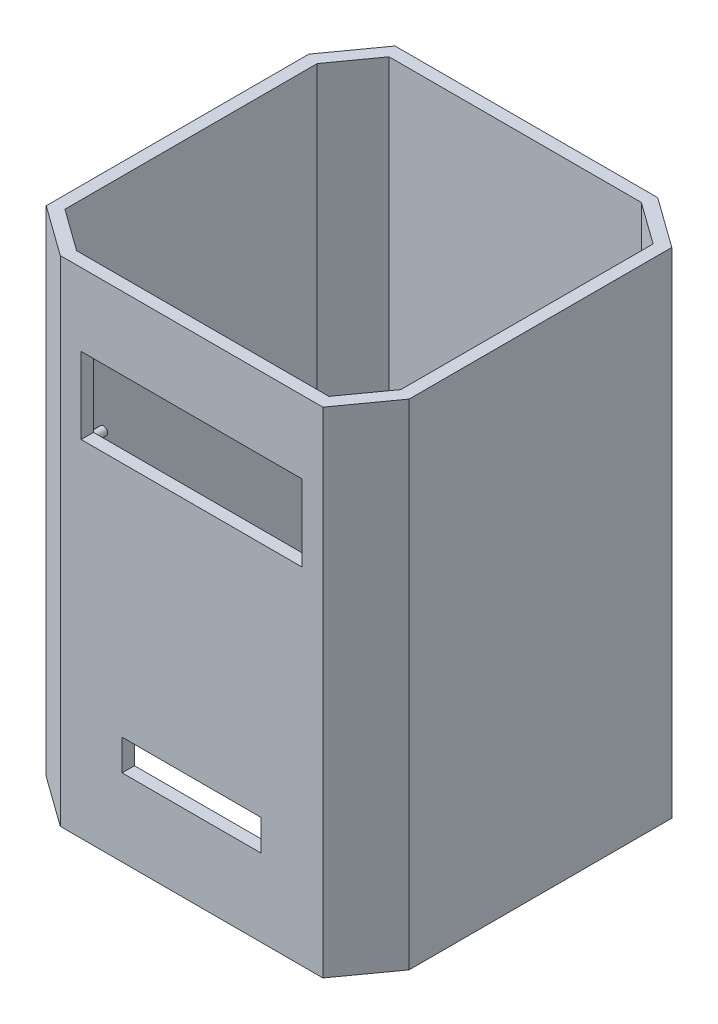
SolidWorks part; units mm, degrees
ref_plane "Front Plane" through (0, 0, 0) normal (0, 0, 1) x (1, 0, 0)
ref_plane "Top Plane" through (0, 0, 0) normal (0, 1, 0) x (1, 0, 0)
ref_plane "Right Plane" through (0, 0, 0) normal (1, 0, 0) x (0, 0, -1)
sketch "Sketch1" plane through (0, 0, 0) normal (0, 1, 0) x (1, 0, 0)
  line L0 (-66.6656, -62.9761) -> (18.3344, -62.9761)
  line L5 (18.3344, -62.9761) -> (30.0152, -46.7417)
  line L6 (30.0152, -46.7417) -> (30.0152, 38.2583)
  line L7 (30.0152, 38.2583) -> (13.7808, 49.9392)
  line L8 (13.7808, 49.9392) -> (-71.2192, 49.9392)
  line L9 (-71.2192, 49.9392) -> (-82.9001, 33.7047)
  line L10 (-82.9001, 33.7047) -> (-82.9001, -51.2953)
  line L11 (-82.9001, -51.2953) -> (-66.6656, -62.9761)
  dimension "D1" = 85
  dimension "D2" = 85
  dimension "D3" = 20
  dimension "D4" = 20
  dimension "D5" = 85
  dimension "D6" = 20
  dimension "D7" = 85
  dimension "D8" = 20
extrude "Boss-Extrude2" add sketch "Sketch1" along normal blind 160
sketch "Sketch10" plane through (0, 160, 0) normal (0, 1, 0) x (1, 0, 0)
  line L16 (-78.9001, -49.2455) -> (-65.3762, -58.9761)
  line L17 (-65.3762, -58.9761) -> (16.2846, -58.9761)
  line L18 (16.2846, -58.9761) -> (26.0152, -45.4522)
  line L19 (26.0152, -45.4522) -> (26.0152, 36.2086)
  line L20 (26.0152, 36.2086) -> (12.4913, 45.9392)
  line L21 (12.4913, 45.9392) -> (-69.1694, 45.9392)
  line L22 (-69.1694, 45.9392) -> (-78.9001, 32.4153)
  line L23 (-78.9001, 32.4153) -> (-78.9001, -49.2455)
  line L24 (-78.9001, -49.2455) -> (-65.3762, -58.9761)
  line L25 (-65.3762, -58.9761) -> (16.2846, -58.9761)
  line L26 (16.2846, -58.9761) -> (26.0152, -45.4522)
  line L27 (26.0152, -45.4522) -> (26.0152, 36.2086)
  line L28 (26.0152, 36.2086) -> (12.4913, 45.9392)
  line L29 (12.4913, 45.9392) -> (-69.1694, 45.9392)
  line L30 (-69.1694, 45.9392) -> (-78.9001, 32.4153)
  line L31 (-78.9001, 32.4153) -> (-78.9001, -49.2455)
  dimension "D1" = 4
extrude "Cut-Extrude3" cut sketch "Sketch10" against normal through all
sketch "Sketch11" plane through (0, 0, 62.9761) normal (0, 0, 1) x (1, 0, 0)
  line L0 (-24.1656, 142.4085) -> (-24.1656, 160) construction
  line L1 (-64.1656, 142.4085) -> (15.8344, 142.4085)
  line L2 (-64.1656, 142.4085) -> (-64.1656, 106.4085)
  line L3 (-64.1656, 106.4085) -> (15.8344, 106.4085)
  line L4 (15.8344, 142.4085) -> (15.8344, 106.4085)
  line L5 (-66.6656, 160) -> (18.3344, 160) construction
  line L6 (-64.1656, 124.4085) -> (40.8079, 124.4085) construction
  line L7 (-24.1656, 142.4085) -> (-24.1656, 95.7276) construction
  circle A0 centre (-61.6656, 139.9085) radius 1.35
  circle A1 centre (13.3344, 139.9085) radius 1.35
  circle A2 centre (13.3344, 108.9085) radius 1.35
  circle A3 centre (-61.6656, 108.9085) radius 1.35
  dimension "D3" = 2.7
  dimension "D4" = 2.5
  dimension "D5" = 2.5
  dimension "D1" = 80
  dimension "D2" = 36
extrude "Boss-Extrude3" add sketch "Sketch11" against normal blind 5 from offset 4 contours A3 | A2 | A1 | A0 region at (13.3344, 139.9085, 62.9761) region at (13.3344, 108.9085, 62.9761) region at (-61.6656, 108.9085, 62.9761) offset against normal yes
sketch "Sketch12" plane through (0, 0, 62.9761) normal (0, 0, 1) x (1, 0, 0)
  line L0 (-24.1656, 136.5085) -> (-24.1656, 142.4085) construction
  line L1 (-59.9156, 136.5085) -> (11.5844, 136.5085)
  line L2 (-59.9156, 136.5085) -> (-59.9156, 111.8085)
  line L3 (-59.9156, 111.8085) -> (11.5844, 111.8085)
  line L4 (11.5844, 136.5085) -> (11.5844, 111.8085)
  line L7 (-64.1656, 142.4085) -> (15.8344, 142.4085) construction
  dimension "D1" = 24.7
  dimension "D2" = 71.5
  dimension "D3" = 5.9
extrude "Cut-Extrude5" cut sketch "Sketch12" against normal up to next
sketch "Sketch14" plane through (0, 0, 62.9761) normal (0, 0, 1) x (1, 0, 0)
  line L0 (-66.6656, 0) -> (18.3344, 0) construction
  line L1 (-46.6656, 35) -> (-1.6656, 35)
  line L2 (-46.6656, 35) -> (-46.6656, 25)
  line L3 (-46.6656, 25) -> (-1.6656, 25)
  line L4 (-1.6656, 35) -> (-1.6656, 25)
  line L7 (-24.1656, 0) -> (-24.1656, 25) construction
  dimension "D1" = 25
  dimension "D2" = 10
  dimension "D3" = 45
extrude "Cut-Extrude7" cut sketch "Sketch14" against normal up to next
